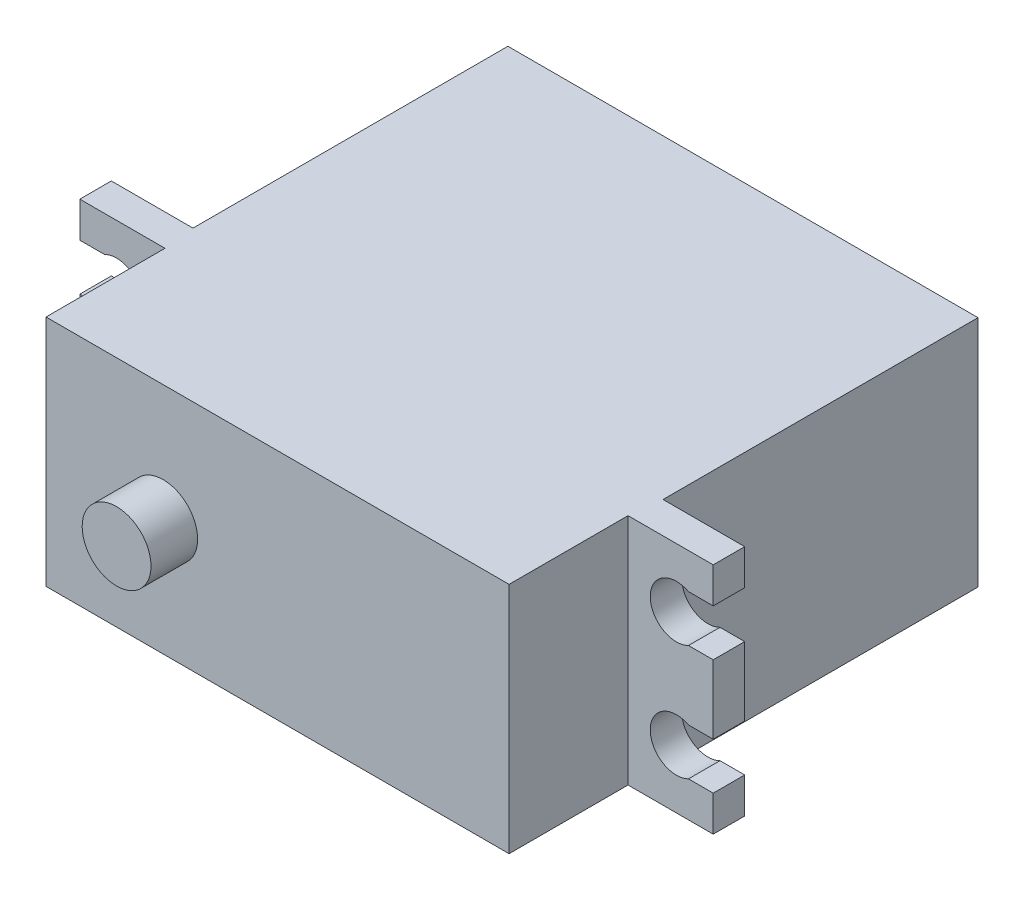
SolidWorks part; units mm, degrees
ref_plane "Front Plane" through (0, 0, 0) normal (0, 0, 1) x (1, 0, 0)
ref_plane "Top Plane" through (0, 0, 0) normal (0, 1, 0) x (1, 0, 0)
ref_plane "Right Plane" through (0, 0, 0) normal (1, 0, 0) x (0, 0, -1)
other "Bounding Box"
ref_plane "Default Plane" through (-8.9266, -12.7485, 0) normal (-0.1736, 0.9848, 0) x (0.9848, 0.1736, 0)
sketch "Sketch1" plane through (0, 0, 0) normal (0, 1, 0) x (1, 0, 0)
  line L1 (20.15, -13.5) -> (-20.15, -13.5)
  line L2 (20.15, -13.5) -> (20.15, 13.5)
  line L3 (20.15, 13.5) -> (-20.15, 13.5)
  line L4 (-20.15, -13.5) -> (-20.15, 13.5)
  line L5 (20.15, -13.5) -> (-20.15, 13.5) construction
  line L6 (20.15, 13.5) -> (-20.15, -13.5) construction
  point P0 (0, 0)
  dimension "D1" = 40.3
  dimension "D2" = 27
extrude "Boss-Extrude1" add sketch "Sketch1" along normal blind 20
sketch "Sketch2" plane through (0, 0, 13.5) normal (0, 0, 1) x (1, 0, 0)
  line L0 (-20.15, 10) -> (20.15, 10) construction
  line L1 (-20.15, 20) -> (-20.15, 0) construction
  line L2 (20.15, 20) -> (20.15, 0) construction
  line L3 (0, 0) -> (0, 20) construction
  line L4 (-20.15, 20) -> (20.15, 20) construction
  line L5 (-20.15, 20) -> (20.15, 20)
  line L6 (27.15, 0) -> (-27.15, 0)
  line L7 (27.15, 0) -> (27.15, 20)
  line L8 (27.15, 20) -> (-27.15, 20)
  line L9 (-27.15, 0) -> (-27.15, 20)
  line L10 (27.15, 0) -> (-27.15, 20) construction
  line L11 (27.15, 20) -> (-27.15, 0) construction
  line L13 (24, 5.05) -> (-24, 5.05)
  line L14 (24, 5.05) -> (24, 14.95)
  line L15 (24, 14.95) -> (-24, 14.95)
  line L16 (-24, 5.05) -> (-24, 14.95)
  line L17 (24, 5.05) -> (-24, 14.95) construction
  line L18 (24, 14.95) -> (-24, 5.05) construction
  line L19 (-24, 12.95) -> (-30.3, 12.95)
  line L20 (-24, 12.95) -> (-24, 16.95)
  line L21 (-24, 16.95) -> (-30.3, 16.95)
  line L22 (-30.3, 12.95) -> (-30.3, 16.95)
  line L23 (-24, 12.95) -> (-30.3, 16.95) construction
  line L24 (-24, 16.95) -> (-30.3, 12.95) construction
  line L29 (-24, 3.05) -> (-30.3, 3.05)
  line L30 (-24, 3.05) -> (-24, 7.05)
  line L31 (-24, 7.05) -> (-30.3, 7.05)
  line L32 (-30.3, 3.05) -> (-30.3, 7.05)
  line L33 (-24, 3.05) -> (-30.3, 7.05) construction
  line L34 (-24, 7.05) -> (-30.3, 3.05) construction
  line L35 (24, 16.95) -> (30.3, 16.95)
  line L36 (24, 16.95) -> (24, 12.95)
  line L37 (24, 12.95) -> (30.3, 12.95)
  line L38 (30.3, 16.95) -> (30.3, 12.95)
  line L39 (24, 16.95) -> (30.3, 12.95) construction
  line L40 (24, 12.95) -> (30.3, 16.95) construction
  line L41 (24, 7.05) -> (30.3, 7.05)
  line L42 (24, 7.05) -> (24, 3.05)
  line L43 (24, 3.05) -> (30.3, 3.05)
  line L44 (30.3, 7.05) -> (30.3, 3.05)
  line L45 (24, 7.05) -> (30.3, 3.05) construction
  line L46 (24, 3.05) -> (30.3, 7.05) construction
  circle A0 centre (-24, 14.95) radius 2.25
  circle A1 centre (-24, 5.05) radius 2.25
  circle A2 centre (24, 5.05) radius 2.25
  circle A3 centre (24, 14.95) radius 2.25
  point P11 (0, 10)
  point P16 (0, 10)
  point P25 (-27.15, 14.95)
  point P30 (-27.15, 5.05)
  point P35 (27.15, 14.95)
  point P40 (27.15, 5.05)
  line M3 (-20.15, 0) -> (20.15, 0)
  line M4 (20.15, 0) -> (20.15, 20)
  line M5 (20.15, 20) -> (-20.15, 20)
  line M6 (-20.15, 20) -> (-20.15, 0)
  dimension "D4" = 4.5
  dimension "D1" = 54.3
  dimension "D2" = 48
  dimension "D3" = 9.9
  dimension "D5" = 4
extrude "Boss-Extrude2" add sketch "Sketch2" along normal blind 2.7 contours L13 M4 M6 M3 | A1 L29 L9 L6 L13 M6 | L15 L13 M4 M6 | A1 L13 L15 A0 L16 M6 | A1 L16 A0 L19 L9 L31 | L15 M4 M5 M6 | A0 L15 L8 L9 L21 M6 | A3 L35 L7 L8 L15 M4 | A3 L14 A2 L41 L7 L37 | A2 L13 L6 L7 L43 M4 | A3 L15 L13 A2 L14 M4 region at (-23.2544, 18.1145, 13.5) region at (0, 17.475, 13.5) region at (23.2544, 18.1145, 13.5) region at (-21.8192, 10, 13.5) region at (0, 10, 13.5) region at (21.8192, 10, 13.5) region at (-23.2544, 1.8855, 13.5) region at (0, 2.525, 13.5) region at (23.2544, 1.8855, 13.5) region at (-25.5976, 10, 13.5) region at (25.5976, 10, 13.5)
sketch "Sketch3" plane through (0, 0, 16.2) normal (0, 0, 1) x (1, 0, 0)
  line L0 (-27.15, 10) -> (27.15, 10) construction
  line L1 (-27.15, 7.05) -> (-27.15, 12.95) construction
  line L2 (27.15, 7.05) -> (27.15, 12.95) construction
  line L3 (0, 20) -> (0, 0) construction
  line L4 (27.15, 20) -> (-27.15, 20) construction
  line L5 (27.15, 20) -> (-27.15, 20)
  line L6 (19.85, 0) -> (-19.85, 0)
  line L7 (19.85, 0) -> (19.85, 20)
  line L8 (19.85, 20) -> (-19.85, 20)
  line L9 (-19.85, 0) -> (-19.85, 20)
  line L10 (19.85, 0) -> (-19.85, 20) construction
  line L11 (19.85, 20) -> (-19.85, 0) construction
  point P11 (0, 10)
  dimension "D2" = 39.7
extrude "Boss-Extrude3" add sketch "Sketch3" along normal blind 10.2 contours L7 L6 L9 L8
sketch "Sketch4" plane through (0, 0, 26.4) normal (0, 0, 1) x (1, 0, 0)
  line L0 (-27.15, 10) -> (27.15, 10) construction
  line L1 (-27.15, 7.05) -> (-27.15, 12.95) construction
  line L2 (27.15, 7.05) -> (27.15, 12.95) construction
  arc A0 (-25.0308, 12.95) -> (-25.0308, 16.95) centre (-24, 14.95) ccw construction
  arc A1 (-25.0308, 12.95) -> (-25.0308, 16.95) centre (-24, 14.95) ccw
  circle A2 centre (-9.8, 10) radius 2.95
  dimension "D2" = 5.9
  dimension "D1" = 14.2
extrude "Boss-Extrude4" add sketch "Sketch4" along normal blind 4 contours A2 L0 | L0 A2 region at (-9.8, 11.252, 26.4) region at (-9.8, 8.748, 26.4)
sketch "Sketch5" plane through (-20.15, 0, 0) normal (-1, 0, 0) x (0, 0, 1)
  line L0 (-13.5, 10) -> (6.1644, 10) construction
  line L1 (-6.9171, 4.3103) -> (-10.4185, 4.3103)
  line L2 (-6.9171, 4.3103) -> (-6.9171, 15.6897)
  line L3 (-6.9171, 15.6897) -> (-10.4185, 15.6897)
  line L4 (-10.4185, 4.3103) -> (-10.4185, 15.6897)
  line L5 (-6.9171, 4.3103) -> (-10.4185, 15.6897) construction
  line L6 (-6.9171, 15.6897) -> (-10.4185, 4.3103) construction
  line L7 (-13.5, 20) -> (-13.5, 0) construction
  point P0 (-8.6678, 10)
  dimension "D1" = 11.3794
  dimension "D2" = 3.5014
  dimension "D3" = 4.8322
extrude "Boss-Extrude5" add sketch "Sketch5" along normal blind 4
